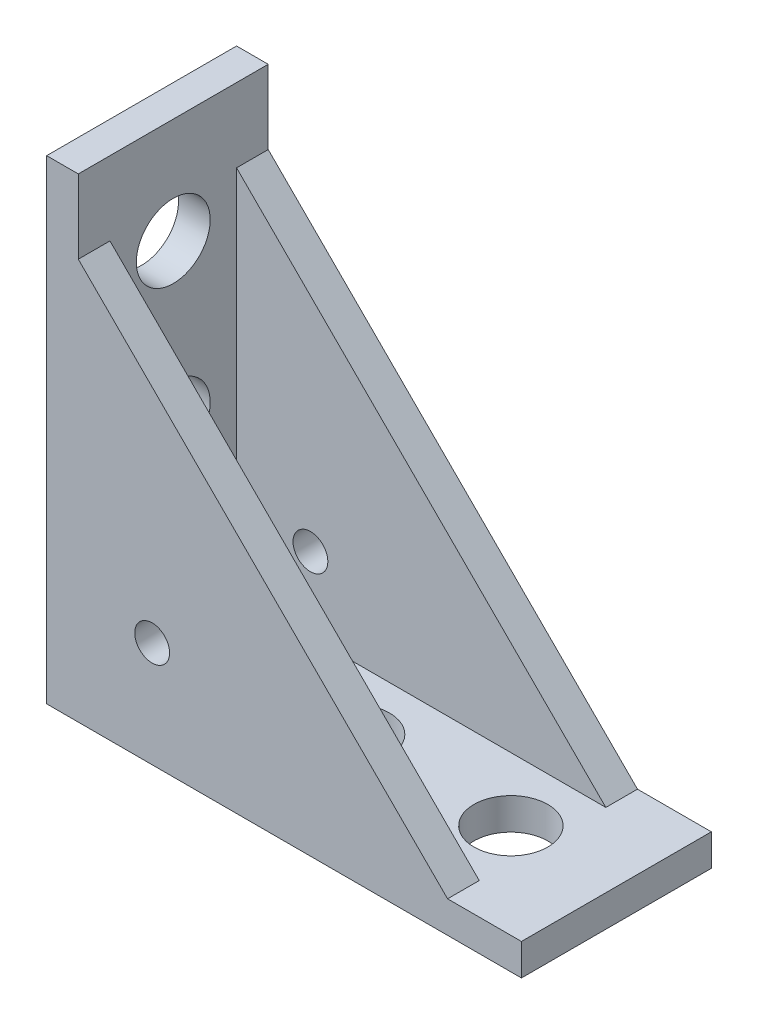
SolidWorks part; units mm, degrees
ref_plane "前视基准面" through (0, 0, 0) normal (0, 0, 1) x (1, 0, 0)
ref_plane "上视基准面" through (0, 0, 0) normal (0, 1, 0) x (1, 0, 0)
ref_plane "右视基准面" through (0, 0, 0) normal (1, 0, 0) x (0, 0, -1)
sketch "草图1" plane through (0, 0, 0) normal (0, 0, 1) x (1, 0, 0)
  line L0 (0, 0) -> (0, 45)
  line L1 (0, 0) -> (45, 0)
  line L2 (0, 45) -> (3, 45)
  line L3 (45, 0) -> (45, 3)
  line L4 (3, 45) -> (3, 38)
  line L5 (3, 38) -> (38, 3)
  line L6 (38, 3) -> (45, 3)
  dimension "D1" = 45
  dimension "D2" = 45
  dimension "D3" = 3
  dimension "D5" = 7
extrude "凸台-拉伸1" add sketch "草图1" along normal mid plane 18
shell "抽壳1" thickness 3 removed face at (20.5, 20.5, 0)
sketch "草图5" plane through (0, 3, 0) normal (0, 1, 0) x (1, 0, 0)
  line L0 (0, 0) -> (45, 0) construction
  line L1 (45, -9) -> (45, 9) construction
  circle A0 centre (20, 0) radius 3.5
  circle A1 centre (35, 0) radius 3.5
  dimension "D3" = 7
  dimension "D1" = 20
  dimension "D2" = 15
extrude "切除-拉伸1" cut sketch "草图5" against normal through all
sketch "草图6" plane through (3, 0, 0) normal (1, 0, 0) x (0, 0, -1)
  line L0 (0, 0) -> (0, 45) construction
  line L1 (-9, 45) -> (9, 45) construction
  line L2 (-9, 0) -> (9, 0) construction
  circle A0 centre (0, 20) radius 3.5
  circle A1 centre (0, 35) radius 3.5
  dimension "D1" = 7
  dimension "D2" = 20
  dimension "D3" = 15
extrude "切除-拉伸2" cut sketch "草图6" against normal through all
hole_wizard "M4 螺纹孔1" positions "草图8" profile "草图7" tap size "M4" standard "GB" end condition through all
sketch "草图8" plane through (0, 0, -9) normal (0, 0, -1) x (-1, 0, 0)
  line L0 (0, 45) -> (0, 0) construction
  line L1 (0, 0) -> (-45, 0) construction
  point P0 (-10, 10)
  dimension "D1" = 10
  dimension "D2" = 10
sketch "草图7" plane through (10, 10, -9) normal (1, 0, 0) x (0, 1, 0)
  line L0 (0, 0) -> (0, 18)
  line L1 (0, 18) -> (1.65, 18)
  line L2 (1.65, 18) -> (1.65, 0)
  line L5 (1.65, 0) -> (0, 0)
  line L11 (0, -6.35) -> (0, 107.95) construction
  dimension "通孔螺纹孔钻头直径" = 3.3
  dimension "通孔螺纹孔钻头深度" = 18
cosmetic thread "孔螺蚊线1" parameters "D2"=4
